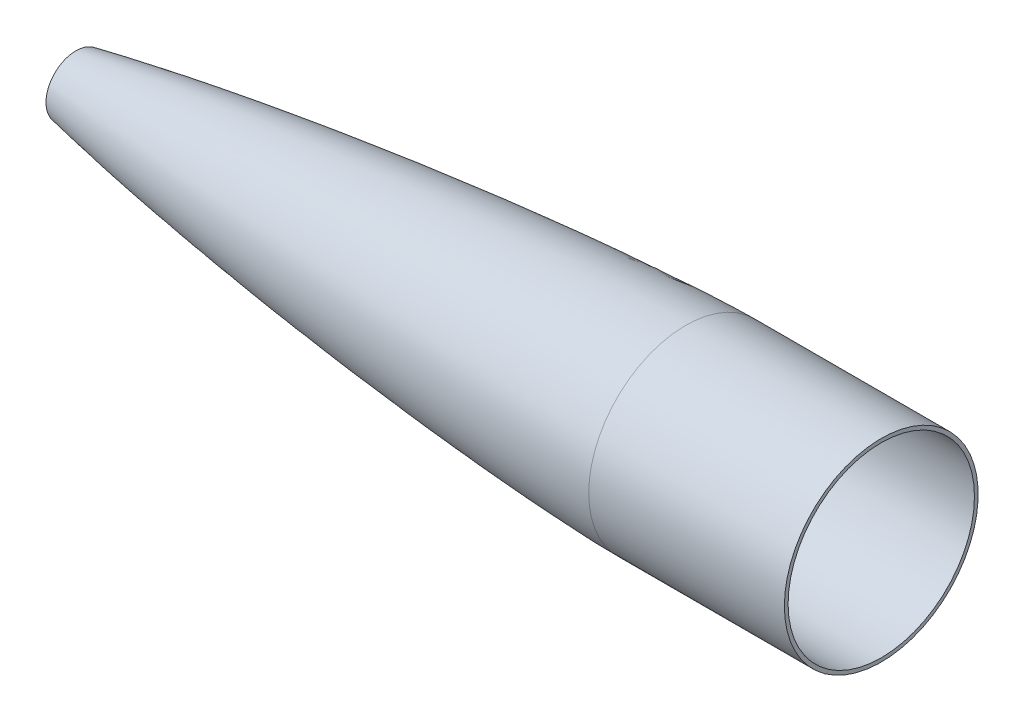
SolidWorks part; units mm, degrees
material "G10 Fiberglass"
ref_plane "Front Plane" through (0, 0, 0) normal (0, 0, 1) x (1, 0, 0)
ref_plane "Top Plane" through (0, 0, 0) normal (0, 1, 0) x (1, 0, 0)
ref_plane "Right Plane" through (0, 0, 0) normal (1, 0, 0) x (0, 0, -1)
sketch "Sketch1" plane through (0, 0, 0) normal (0, 0, 1) x (1, 0, 0)
  line L1 (0, 0) -> (294.4368, 0)
  line L6 (294.4368, 0) -> (374.6501, 0)
  line L7 (374.6501, 0) -> (374.6501, 39.7256)
  line L8 (374.6501, 39.7256) -> (294.4368, 39.7256)
  spline S0 degree 4 poles (0, 0) (0.0019, 0.0062) (0.0066, 0.0182) (0.0202, 0.0404) (0.052, 0.0813) (0.0986, 0.1299) (0.16, 0.1855) (0.2485, 0.2577) (0.3706, 0.348) (0.5569, 0.4725) (0.8721, 0.6619) (1.4039, 0.947) (2.3337, 1.3873) (4.0188, 2.0868) (7.0558, 3.1796) (12.0854, 4.7438) (21.1448, 7.1909) (33.9407, 10.1499) (49.8184, 13.3765) (68.0431, 16.6773) (86.3497, 19.694) (104.6942, 22.4707) (123.0687, 25.0401) (141.4687, 27.4206) (159.8906, 29.624) (178.3323, 31.6557) (196.792, 33.5162) (215.2687, 35.201) (233.7615, 36.6987) (252.2699, 37.9897) (267.9572, 38.8762) (279.9188, 39.389) (288.1478, 39.6307) (291.7413, 39.7002) (293.5383, 39.7228) (294.4368, 39.7256) knots 0 0 0 0 0 0.000087 0.000174 0.000347 0.000695 0.00099 0.001284 0.001879 0.002733 0.003996 0.006219 0.009974 0.016536 0.028475 0.049524 0.080651 0.142462 0.204716 0.266969 0.329223 0.391477 0.453731 0.515984 0.578238 0.640492 0.702745 0.764999 0.827253 0.889506 0.95176 0.97588 0.98794 1 1 1 1 1 construction
  spline S1 degree 4 poles (0, 0) (0.0019, 0.0062) (0.0066, 0.0182) (0.0202, 0.0404) (0.052, 0.0813) (0.0986, 0.1299) (0.16, 0.1855) (0.2485, 0.2577) (0.3706, 0.348) (0.5569, 0.4725) (0.8721, 0.6619) (1.4039, 0.947) (2.3337, 1.3873) (4.0188, 2.0868) (7.0558, 3.1796) (12.0854, 4.7438) (21.1448, 7.1909) (33.9407, 10.1499) (49.8184, 13.3765) (68.0431, 16.6773) (86.3497, 19.694) (104.6942, 22.4707) (123.0687, 25.0401) (141.4687, 27.4206) (159.8906, 29.624) (178.3323, 31.6557) (196.792, 33.5162) (215.2687, 35.201) (233.7615, 36.6987) (252.2699, 37.9897) (267.9572, 38.8762) (279.9188, 39.389) (288.1478, 39.6307) (291.7413, 39.7002) (293.5383, 39.7228) (294.4368, 39.7256) knots 0 0 0 0 0 0.000087 0.000174 0.000347 0.000695 0.00099 0.001284 0.001879 0.002733 0.003996 0.006219 0.009974 0.016536 0.028475 0.049524 0.080651 0.142462 0.204716 0.266969 0.329223 0.391477 0.453731 0.515984 0.578238 0.640492 0.702745 0.764999 0.827253 0.889506 0.95176 0.97588 0.98794 1 1 1 1 1
  dimension "D1" = 80.2133
  dimension "D2" = 39.7256
  dimension "D3" = 294.4368
ref_axis "Axis1" through (-19.05, 0, 0) along (1, 0, 0)
revolve "Revolve1" add sketch "Sketch1" angle 360 about axis through (-19.05, 0, 0) along (1, 0, 0)
shell "Shell1" thickness 1.524 removed face at (374.6501, 0, 39.7256)
ref_plane "Plane1" through (44.4501, 0, 0) normal (1, 0, 0) x (0, 0, -1)
sketch "Sketch6" plane through (44.4501, 0, 0) normal (1, 0, 0) x (0, 0, -1)
  circle A1 centre (0, 0) radius 14.5845
extrude "Cut-Extrude1" cut sketch "Sketch6" against normal blind 98.044
ref_plane "Plane2" through (294.4369, 0, 0) normal (1, 0, 0) x (0, 0, -1)
